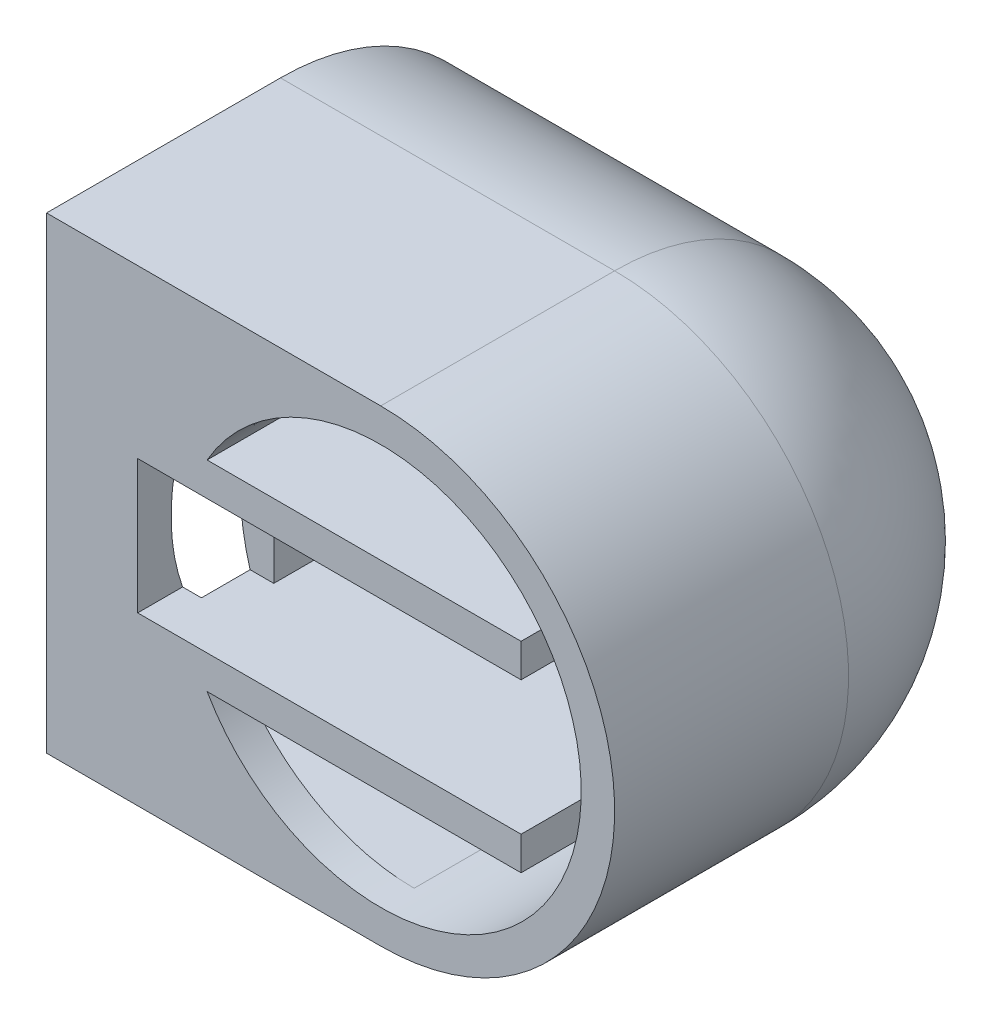
SolidWorks part; units mm, degrees
ref_plane "Front Plane" through (0, 0, 0) normal (0, 0, 1) x (1, 0, 0)
ref_plane "Top Plane" through (0, 0, 0) normal (0, 1, 0) x (1, 0, 0)
ref_plane "Right Plane" through (0, 0, 0) normal (1, 0, 0) x (0, 0, -1)
sketch "Sketch3" plane through (0, 0, 0) normal (1, 0, 0) x (0, 0, -1)
  circle A0 centre (0, 0) radius 30
  circle A1 centre (0, 0) radius 35
extrude "Boss-Extrude1" add sketch "Sketch3" along normal blind 50
sketch "Sketch4" plane through (50, 0, 0) normal (1, 0, 0) x (0, 0, -1)
  circle A0 centre (0, 0) radius 30
extrude "Boss-Extrude2" add sketch "Sketch4" against normal blind 5
sketch "Sketch5" plane through (50, 0, 0) normal (1, 0, 0) x (0, 0, -1)
  line L0 (0, -35) -> (0, 35)
  circle A0 centre (0, 0) radius 35 construction
  arc A1 (0, -35) -> (0, 35) centre (0, 0) ccw
revolve "Revolve1" add sketch "Sketch5" angle 90 about L0 reverse direction yes
shell "Shell1" thickness 5 removed face at (67.5, 0, 0)
sketch "Sketch7" plane through (0, 0, 0) normal (0, 0, 1) x (1, 0, 0)
  line L0 (65.4352, 0) -> (65.4352, 10)
  line L1 (50, -35) -> (50, 35) construction
  line L2 (65.4352, 10) -> (25.4352, 10)
  line L3 (65.4352, 10) -> (65.4352, -10)
  line L4 (65.4352, -10) -> (25.4352, -10)
  line L5 (25.4352, 10) -> (25.4352, -10)
  line L7 (25.4352, -10) -> (20.4352, -10)
  line L8 (25.4352, -10) -> (25.4352, -15)
  line L9 (25.4352, -15) -> (20.4352, -15)
  line L10 (20.4352, -10) -> (20.4352, -15)
  line L11 (25.4352, -10) -> (20.4352, -10)
  line L12 (25.4352, -10) -> (25.4352, 10)
  line L13 (25.4352, 10) -> (20.4352, 10)
  line L14 (20.4352, -10) -> (20.4352, 10)
  line L15 (65.4352, -10) -> (78.2843, -10)
  line L16 (65.4352, -10) -> (65.4352, 10)
  line L17 (65.4352, 10) -> (78.2843, 10)
  line L18 (78.2843, -10) -> (78.2843, 10)
  circle A0 centre (50, 0) radius 30
  circle A1 centre (50, 0) radius 30
  dimension "D4" = 5
  dimension "D7" = 60
  dimension "D1" = 10
  dimension "D2" = 20
  dimension "D3" = 40
  dimension "D5" = 5
  dimension "D6" = 12.8491
sketch "Sketch8" plane through (45, 0, 0) normal (-1, 0, 0) x (0, 0, 1)
  line L0 (0, 0) -> (-26, 0)
  line L1 (0, -10) -> (0, 10) construction
  line L2 (-26, 0) -> (-26, 14.9666)
  line L3 (-26, 14.9666) -> (-26, -14.9666)
  circle A0 centre (0, 0) radius 30 construction
  circle A1 centre (0, 0) radius 30
  circle M3 centre (0, 0) radius 30
  dimension "D1" = 26
extrude "Cut-Extrude2" cut sketch "Sketch8" against normal blind 5 contours L3 L2 M3 | L3 L2 M3 region at (45, 0, -27.6095) region at (45, 0, 0.8138)
extrude "Boss-Extrude4" add sketch "Sketch7" against normal up to surface (23.7014 mm away) contours L15 L18 L17 L0 L3 region at (71.8597, 0, 0) up to face at (65, 0, -15)
sketch "Sketch10" plane through (0, 0, 0) normal (0, 0, 1) x (1, 0, 0)
  line L0 (50, -30) -> (50, 30) construction
  line L1 (50, 35) -> (50, -35)
  arc A0 (50, 30) -> (50, -30) centre (50, 0) ccw
  arc A1 (50, 35) -> (50, -35) centre (50, 0) ccw
  line M2 (50, -30) -> (50, -35)
  line M4 (50, 35) -> (50, 30)
  dimension "D2" = 60
extrude "Boss-Extrude5" add sketch "Sketch10" along normal up to surface contours A1 A0 M4 M2 region at (49.2174, 32.5, 0) up to face at (0, 0, -30)
sketch "Sketch12" plane through (0, 0, 0) normal (0, 0, 1) x (1, 0, 0)
  line L0 (50, -30) -> (50, 30) construction
  line L1 (50, 35) -> (50, -35)
  circle A0 centre (50, 0) radius 30
  circle A1 centre (50, 0) radius 35
  arc M2 (78.2843, -10) -> (50, -30) centre (50, 0) cw
  line M3 (50, -30) -> (50, -35)
  arc M4 (50, -35) -> (50, 35) centre (50, 0) ccw
  line M5 (50, 35) -> (50, 30)
  arc M6 (50, 30) -> (78.2843, 10) centre (50, 0) cw
  arc M7 (78.2843, 10) -> (78.2843, -10) centre (50, 0) cw
extrude "Boss-Extrude18" add sketch "Sketch12" along normal up to vertex contours M7 M2 M3 M4 M5 M6 region at (74.1953, 24.1953, 0) up to point (50, 0, 35)
sketch "Sketch13" plane through (50, 0, 0) normal (-1, 0, 0) x (0, 0, 1)
  line L1 (35, -35) -> (0, -35)
  line L2 (35, -35) -> (35, -30)
  line L3 (35, -30) -> (0, -30)
  line L4 (0, -35) -> (0, -30)
  line L5 (35, 35) -> (0, 35)
  line L6 (35, 35) -> (35, 30)
  line L7 (35, 30) -> (0, 30)
  line L8 (0, 35) -> (0, 30)
extrude "Boss-Extrude19" add sketch "Sketch13" along normal up to surface (50 mm away) up to face at (0, 0, -35)
sketch "Sketch14" plane through (0, -30, 0) normal (0, 1, 0) x (1, 0, 0)
  line L0 (50, -35) -> (50, -18.0278) construction
  line L1 (0, -35) -> (50, -35)
  line L2 (0, -35) -> (0, -30)
  line L3 (0, -30) -> (50, -30)
  line L4 (50, -35) -> (50, -30)
  dimension "D1" = 5
extrude "Boss-Extrude20" add sketch "Sketch14" along normal up to surface (60 mm away) up to face at (25, 30, 26.5139)
sketch "Sketch15" plane through (0, 0, 35) normal (0, 0, 1) x (1, 0, 0)
  line L0 (50, -30) -> (50, 30) construction
  circle A0 centre (50, 0) radius 30
extrude "Cut-Extrude4" cut sketch "Sketch15" against normal blind 25
sketch "Sketch16" plane through (0, 0, 35) normal (0, 0, 1) x (1, 0, 0)
  line L0 (20, 0) -> (50, 0)
  line L14 (20, 10) -> (66, 10)
  line L15 (20, 10) -> (20, -10)
  line L16 (20, -10) -> (66, -10)
  line L17 (66, 10) -> (66, -10)
  line L18 (17.9331, -15) -> (82.0669, -15)
  line L19 (15, 5.3187) -> (15, -5.3187)
  line L20 (17.9331, 15) -> (82.0669, 15)
  line L21 (71, -28.5007) -> (71, 28.5007)
  arc A0 (71, 28.5007) -> (82.0669, 15) centre (50, 0) ccw
  arc A2 (17.9331, 15) -> (15, -5.3187) centre (50, 0) ccw
  arc A3 (82.0669, -15) -> (71, -28.5007) centre (50, 0) ccw
  arc A4 (15, 5.3187) -> (17.9331, -15) centre (50, 0) ccw
  circle A5 centre (50, 0) radius 30 construction
  point P14 (20, 0)
  circle M7 centre (50, 0) radius 30
  dimension "D1" = 46
  dimension "D2" = 20
  dimension "D3" = 5
  dimension "D4" = 5
  dimension "D5" = 5
  dimension "D6" = 5
sketch "Sketch19" plane through (0, 0, 35) normal (0, 0, 1) x (1, 0, 0)
  line L0 (50, -30) -> (50, 30) construction
  line L1 (20, 10) -> (66, 10)
  line L2 (20, 10) -> (20, -10)
  line L3 (20, -10) -> (66, -10)
  line L4 (66, 10) -> (66, -10)
  line L9 (50, 0) -> (20, 0)
  circle A0 centre (50, 0) radius 30
  arc A3 (29.4798, -8.5311) -> (29.4875, -8.508) centre (3.8893, 0) ccw
  point P17 (20, 0)
extrude "Cut-Extrude6" cut sketch "Sketch16" against normal blind 40 and the other way through all contours L14 L15 M7 | L15 L16 M7 region at (20.5121, 7.5145, 35) region at (20.5121, -7.5145, 35)
extrude "Boss-Extrude21" add sketch "Sketch16<17>" against normal blind 32 contours L18 L21 L20 L14 L17 L16 M7 region at (23.2766, 12.3115, 35)
sketch "Sketch16<17>" plane through (0, 0, 35) normal (0, 0, 1) x (1, 0, 0) same geometry as "Sketch16"
sketch "Sketch20" plane through (0, 0, 35) normal (0, 0, 1) x (1, 0, 0)
  line L0 (71, -15) -> (71, 15) construction
  line L1 (20, 10) -> (13.641, 10)
  line L2 (20, 10) -> (20, -10.1194)
  line L3 (20, -10.1194) -> (13.641, -10.1194)
  line L4 (13.641, 10) -> (13.641, -10.1194)
  line L5 (13.641, 10) -> (71, 10)
  line L6 (13.641, 10) -> (13.641, -10)
  line L7 (13.641, -10) -> (71, -10)
  line L8 (71, 10) -> (71, -10)
  line L9 (65.4352, -10) -> (78.2843, -10) construction
  line M1 (66, 10) -> (66, -10)
  line M2 (66, -10) -> (20, -10)
  line M3 (20, -10) -> (20, 10)
  line M4 (20, 10) -> (66, 10)
  line M7 (71, -15) -> (71, 15)
extrude "Cut-Extrude7" cut sketch "Sketch20" against normal blind 14 contours L4 L7 L1 M3 | M1 M4 M3 M2 | L7 L5 M1 M7 region at (16.8205, 0, 35) region at (43, 0, 35) region at (68.5, 0, 35)
sketch "Sketch21" plane through (0, 0, 0) normal (-1, 0, 0) x (0, 0, 1)
  circle A0 centre (0, 0) radius 30
  circle A1 centre (0, 0) radius 56.3596
  circle A2 centre (0, 0) radius 35
sketch "Sketch23" plane through (0, 35, 0) normal (0, 1, 0) x (1, 0, 0)
  line L0 (0, 0) -> (85, 0)
